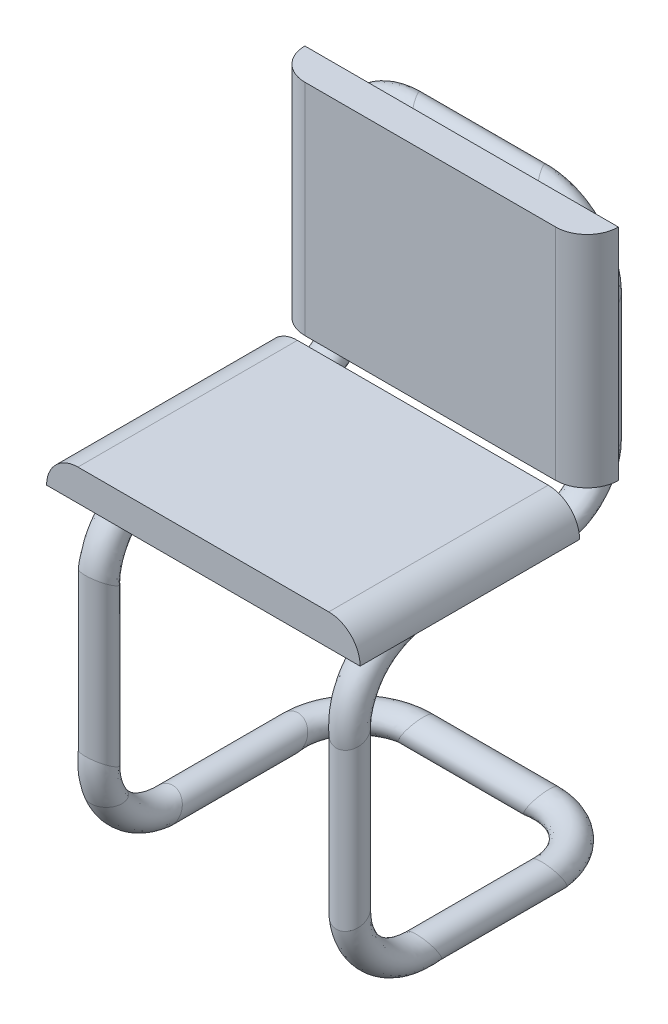
SolidWorks part; units mm, degrees
ref_plane "前视基准面" through (0, 0, 0) normal (0, 0, 1) x (1, 0, 0)
ref_plane "上视基准面" through (0, 0, 0) normal (0, 1, 0) x (1, 0, 0)
ref_plane "右视基准面" through (0, 0, 0) normal (1, 0, 0) x (0, 0, -1)
sketch3d "3D草图1"
  line L0 (-40, 20, 80) -> (-40, 70, 80)
  line L1 (-40, 90, 60) -> (-40, 90, 20)
  line L2 (-40, 110, 0) -> (-40, 150, 0)
  line L3 (-20, 170, 0) -> (20, 170, 0)
  line L4 (40, 150, 0) -> (40, 110, 0)
  line L5 (40, 90, 20) -> (40, 90, 60)
  line L6 (40, 70, 80) -> (40, 20, 80)
  line L7 (40, 0, 60) -> (40, 0, 20)
  line L8 (20, 0, 0) -> (-20, 0, 0)
  line L9 (-40, 0, 60) -> (-40, 0, 20)
  arc A0 (-20, 0, 0) -> (-40, 0, 20) centre (-20, 0, 20) ccw
  arc A1 (40, 0, 20) -> (20, 0, 0) centre (20, 0, 20) ccw
  arc A2 (40, 20, 80) -> (40, 0, 60) centre (40, 20, 60) ccw
  arc A3 (40, 90, 60) -> (40, 70, 80) centre (40, 70, 60) ccw
  arc A4 (40, 110, 0) -> (40, 90, 20) centre (40, 110, 20) ccw
  arc A5 (20, 170, 0) -> (40, 150, 0) centre (20, 150, 0) ccw
  arc A6 (-40, 150, 0) -> (-20, 170, 0) centre (-20, 150, 0) ccw
  arc A7 (-40, 90, 20) -> (-40, 110, 0) centre (-40, 110, 20) ccw
  arc A8 (-40, 70, 80) -> (-40, 90, 60) centre (-40, 70, 60) ccw
  arc A9 (-40, 20, 80) -> (-40, 0, 60) centre (-40, 20, 60) ccw
  point P12 (-40, 0, 0)
  point P13 (-20, 20, 20)
  point P16 (40, 0, 0)
  point P17 (20, 20, 20)
  point P20 (40, 0, 80)
  point P21 (60, 20, 60)
  point P24 (40, 90, 80)
  point P25 (60, 70, 60)
  point P28 (40, 90, 0)
  point P29 (20, 110, 20)
  point P32 (40, 170, 0)
  point P33 (20, 150, -20)
  point P36 (-40, 170, 0)
  point P37 (-20, 150, -20)
  point P40 (-40, 90, 0)
  point P41 (-20, 110, 20)
  point P44 (-40, 90, 80)
  point P45 (-60, 70, 60)
  point P48 (-40, 0, 80)
  point P49 (-20, 20, 60)
  point P50 (0, 0, 0)
  dimension "D10" = 20
  dimension "D1" = 90
  dimension "D2" = 80
  dimension "D3" = 80
  dimension "D4" = 80
  dimension "D5" = 80
  dimension "D6" = 80
  dimension "D7" = 90
  dimension "D8" = 80
  dimension "D9" = 80
ref_plane "基准面1" through (0, 10, 0) normal (0, 1, 0) x (1, 0, 0)
sketch "草图1" plane through (0, 10, 0) normal (0, 1, 0) x (1, 0, 0)
  circle A0 centre (-40, -80) radius 5
  dimension "D1" = 10
sweep "扫描1" add profiles "草图1" path "3D草图1"
ref_plane "基准面2" through (0, 90, 0) normal (0, 1, 0) x (1, 0, 0)
ref_plane "基准面3" through (0, 95, 0) normal (0, 1, 0) x (1, 0, 0)
sketch "草图3" plane through (0, 95, 0) normal (0, 1, 0) x (1, 0, 0)
  line L1 (0, 21.3778) -> (0, -111.8816) construction
  line L6 (-50, -89.0552) -> (50, -89.0552)
  line L7 (50, -19.0552) -> (50, -89.0552)
  line L8 (-50, -19.0552) -> (-50, -89.0552)
  line L9 (-50, -19.0552) -> (50, -19.0552)
  point P1 (0, -19.0552)
  dimension "D1" = 70
  dimension "D2" = 100
extrude "凸台-拉伸1" add sketch "草图3" along normal blind 10
ref_plane "基准面5" through (0, 0, 6.67) normal (0, 0, 1) x (1, 0, 0)
sketch "草图4" plane through (0, 0, 6.67) normal (0, 0, 1) x (1, 0, 0)
  line L0 (0, 54.7138) -> (0, 25.719) construction
  line L2 (-50, 175.1101) -> (50, 175.1101)
  line L3 (-50, 175.1101) -> (-50, 105.1101)
  line L4 (-50, 105.1101) -> (50, 105.1101)
  line L5 (50, 175.1101) -> (50, 105.1101)
  point P7 (0, 175.1101)
  dimension "D1" = 70
  dimension "D2" = 100
extrude "凸台-拉伸2" add sketch "草图4" along normal blind 10
fillet "圆角1" radius 10 4 edges at (-50, 105, 54.0552) (50, 105, 54.0552) (50, 140.1101, 16.67) (-50, 140.1101, 16.67)
